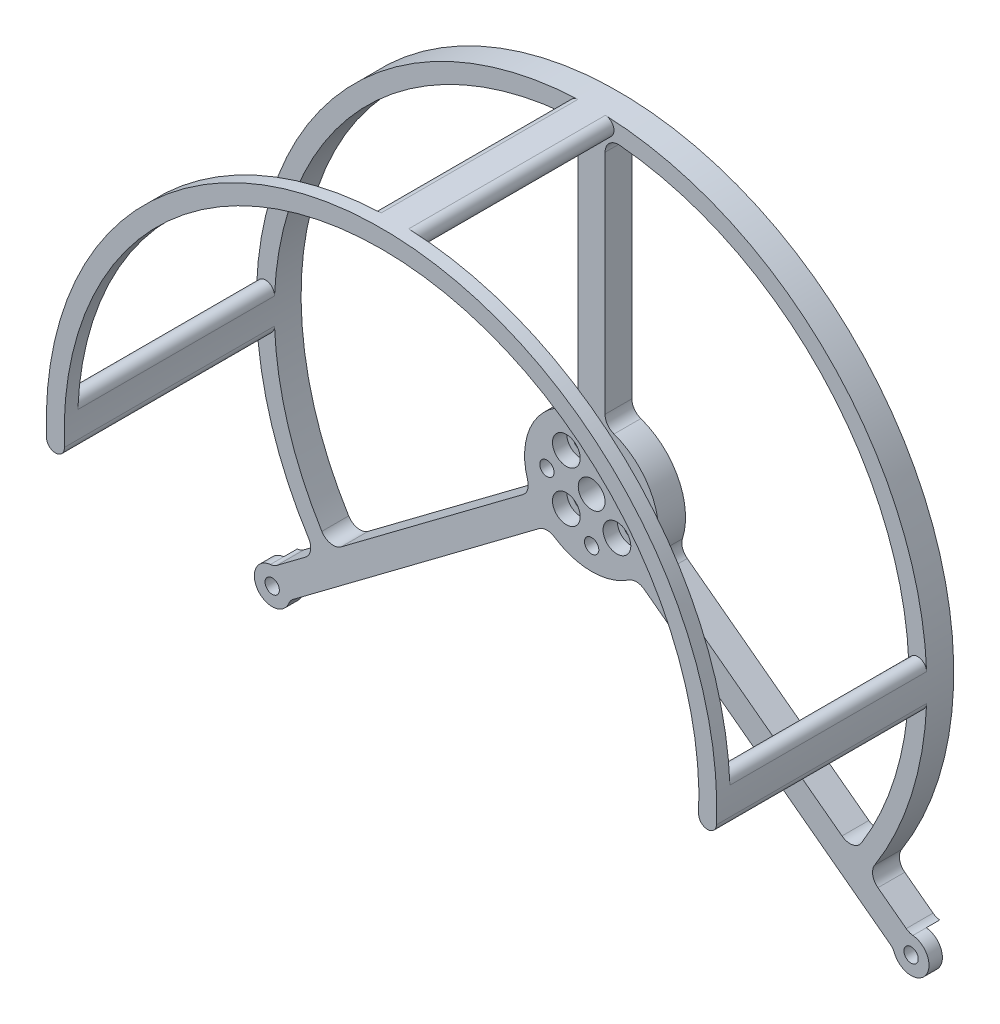
SolidWorks part; units mm, degrees
ref_plane "前视基准面" through (0, 0, 0) normal (0, 0, 1) x (1, 0, 0)
ref_plane "上视基准面" through (0, 0, 0) normal (0, 1, 0) x (1, 0, 0)
ref_plane "右视基准面" through (0, 0, 0) normal (1, 0, 0) x (0, 0, -1)
sketch "草图1" plane through (0, 0, 0) normal (0, 0, 1) x (1, 0, 0)
  line L0 (0, 0) -> (10, 0) construction
  line L1 (0, 0) -> (0, -10) construction
  line L2 (0, 0) -> (5.6569, -5.6569) construction
  circle A0 centre (0, 0) radius 15
  circle A1 centre (0, 0) radius 8 construction
  circle A2 centre (0, 0) radius 10 construction
  circle A3 centre (5.6569, -5.6569) radius 1.6
  circle A4 centre (-5.6569, -5.6569) radius 1.6
  circle A5 centre (5.6569, 5.6569) radius 1.6
  circle A6 centre (-5.6569, 5.6569) radius 1.6
  circle A7 centre (0, -10) radius 1.6
  circle A8 centre (10, 0) radius 1.6
  circle A9 centre (-10, 0) radius 1.6
  circle A10 centre (0, 10) radius 1.6
  dimension "D1" = 30
  dimension "D2" = 16
  dimension "D3" = 20
  dimension "D5" = 3.2
  dimension "D6" = 3.2
extrude "凸台-拉伸1" add sketch "草图1" along normal blind 6
sketch "草图2" plane through (0, 0, 6) normal (0, 0, 1) x (1, 0, 0)
  line L0 (0, 0) -> (8, 0) construction
  line L1 (0, 0) -> (0, -8) construction
  circle A0 centre (0, 0) radius 8 construction
  circle A1 centre (5.6569, 5.6569) radius 3.1
  circle A2 centre (5.6569, -5.6569) radius 3.1
  circle A3 centre (-5.6569, -5.6569) radius 3.1
  circle A4 centre (-5.6569, 5.6569) radius 3.1
  dimension "D1" = 6.2
extrude "切除-拉伸1" cut sketch "草图2" against normal blind 3.2
sketch "草图4" plane through (0, 0, 0) normal (0, 0, -1) x (-1, 0, 0)
  circle A0 centre (0, 0) radius 3
  dimension "D1" = 6
extrude "切除-拉伸2" cut sketch "草图4" against normal blind 8
sketch "草图3" plane through (0, 0, 0) normal (0, 0, -1) x (-1, 0, 0)
  line L0 (0, 0) -> (15, 0) construction
  line L1 (0, 0) -> (55.2216, -41.3712) construction
  line L5 (13.5609, -6.4111) -> (76.4213, -53.5052)
  line L9 (9.9634, -11.213) -> (72.8238, -58.3071)
  line L10 (76.4213, -53.5052) -> (72.8238, -58.3071)
  circle A0 centre (0, 0) radius 66 construction
  circle A1 centre (0, 0) radius 69 construction
  circle A3 centre (0, 0) radius 15 construction
  circle A4 centre (0, 0) radius 15
  circle M4 centre (0, 0) radius 15
  dimension "D1" = 132
  dimension "D2" = 138
  dimension "D3" = 30
  dimension "D5" = 93.29
  dimension "D4" = 3
  dimension "D6" = 36.84
extrude "凸台-拉伸3" add sketch "草图3" against normal blind 6 contours L10 L5 L9 M4 region at (-43.2733, -32.4197, 0)
sketch "草图5" plane through (0, 0, 0) normal (0, 0, -1) x (-1, 0, 0)
  line L0 (0, 0) -> (74.6226, -55.9061) construction
  line L1 (76.4213, -53.5052) -> (72.8238, -58.3071) construction
  circle A0 centre (71.4599, -53.5367) radius 1.6
  circle A1 centre (0, 0) radius 3 construction
  dimension "D1" = 3.2
  dimension "D2" = 89.29
extrude "切除-拉伸3" cut sketch "草图5" against normal blind 6
mirror "镜向2" about plane through (0, 0, 0) normal (1, 0, 0) of "切除-拉伸3", "凸台-拉伸3"
sketch "草图6" plane through (0, 0, 0) normal (0, 0, -1) x (-1, 0, 0)
  circle A0 centre (-71.4599, -53.5367) radius 4
  circle A1 centre (-71.4599, -53.5367) radius 1.6
  circle A2 centre (71.4599, -53.5367) radius 1.6
  circle A3 centre (71.4599, -53.5367) radius 4
  dimension "D1" = 8
  dimension "D2" = 3.2
  dimension "D3" = 8
  dimension "D4" = 3.2
extrude "凸台-拉伸4" add sketch "草图6" against normal blind 6
sketch "草图7" plane through (0, 0, 0) normal (0, 0, -1) x (-1, 0, 0)
  line L0 (-75.3761, -52.7221) -> (-79.5868, -53.5367)
  line L1 (-79.5868, -53.5367) -> (-72.314, -61.4299)
  line L2 (-72.314, -61.4299) -> (-71.8903, -57.5135)
  line L3 (71.7786, -57.524) -> (73.2525, -62.4618)
  line L4 (73.2525, -62.4618) -> (79.8511, -53.0431)
  line L5 (79.8511, -53.0431) -> (75.3761, -52.7221)
  arc A0 (-75.3761, -52.7221) -> (-71.8903, -57.5135) centre (-71.4599, -53.5367) ccw
  arc A1 (71.7786, -57.524) -> (75.3761, -52.7221) centre (71.4599, -53.5367) ccw
extrude "切除-拉伸4" cut sketch "草图7" against normal blind 6 contours A1 L5 L4 L3 | A0 L2 L1 L0
sketch "草图8" plane through (0, 0, 0) normal (0, 0, -1) x (-1, 0, 0)
  line L0 (-58.5702, -40.1314) -> (-61.7742, -42.5318)
  line L1 (-13.5609, -6.4111) -> (-71.1413, -49.5494) construction
  line L2 (61.7742, -42.5318) -> (58.5702, -40.1314)
  line L3 (13.5609, -6.4111) -> (71.1413, -49.5494) construction
  circle A0 centre (0, 0) radius 89.29 construction
  arc A1 (61.7742, -42.5318) -> (-61.7742, -42.5318) centre (0, 0) ccw
  arc A2 (58.5702, -40.1314) -> (-58.5702, -40.1314) centre (0, 0) ccw
  dimension "D1" = 150
  dimension "D2" = 142
extrude "凸台-拉伸5" add sketch "草图8" against normal blind 6
sketch "草图9" plane through (0, 0, 0) normal (0, 0, -1) x (-1, 0, 0)
  line L0 (0, 0) -> (0, 71) construction
  line L1 (-3, 14.6969) -> (-3, 70.9366)
  line L2 (3, 14.6969) -> (3, 70.9366)
  arc A0 (58.5702, -40.1314) -> (-58.5702, -40.1314) centre (0, 0) ccw construction
  arc A1 (13.5609, -6.4111) -> (-13.5609, -6.4111) centre (0, 0) ccw construction
  arc A2 (3, 14.6969) -> (-3, 14.6969) centre (0, 0) ccw
  arc A3 (3, 70.9366) -> (-3, 70.9366) centre (0, 0) ccw
  dimension "D1" = 3
extrude "凸台-拉伸6" add sketch "草图9" against normal blind 6
sketch "草图10" plane through (0, 0, 6) normal (0, 0, 1) x (1, 0, 0)
  line L0 (0, 0) -> (-73, 0) construction
  line L1 (-73, 0) -> (-75, 0) construction
  arc A0 (-72.8288, 4.997) -> (-72.8288, -4.997) centre (0, 0) ccw construction
  arc A1 (-74.9366, 3.0822) -> (-74.9366, -3.0822) centre (0, 0) ccw
  arc A10 (-70.94, 2.9178) -> (-70.94, -2.9178) centre (0, 0) ccw
  arc A11 (-70.94, 2.9178) -> (-74.9366, 3.0822) centre (-72.9383, 3) ccw
  arc A12 (-70.94, -2.9178) -> (-74.9366, -3.0822) centre (-72.9383, -3) cw
  arc A13 (2.9178, 70.94) -> (-2.9178, 70.94) centre (0, 0) ccw
  arc A14 (-2.9178, 70.94) -> (-3.0822, 74.9366) centre (-3, 72.9383) cw
  arc A15 (3.0822, 74.9366) -> (-3.0822, 74.9366) centre (0, 0) ccw
  arc A16 (2.9178, 70.94) -> (3.0822, 74.9366) centre (3, 72.9383) ccw
  arc A17 (70.94, -2.9178) -> (70.94, 2.9178) centre (0, 0) ccw
  arc A18 (70.94, 2.9178) -> (74.9366, 3.0822) centre (72.9383, 3) cw
  arc A19 (74.9366, -3.0822) -> (74.9366, 3.0822) centre (0, 0) ccw
  arc A20 (70.94, -2.9178) -> (74.9366, -3.0822) centre (72.9383, -3) ccw
  arc A25 (-2.9178, -70.94) -> (2.9178, -70.94) centre (0, 0) ccw [skipped]
  arc A26 (2.9178, -70.94) -> (3.0822, -74.9366) centre (3, -72.9383) cw [skipped]
  arc A27 (-3.0822, -74.9366) -> (3.0822, -74.9366) centre (0, 0) ccw [skipped]
  arc A28 (-2.9178, -70.94) -> (-3.0822, -74.9366) centre (-3, -72.9383) ccw [skipped]
  point P33 (0, 0)
  dimension "D1" = 146
  dimension "D2" = 3
  dimension "D3" = 71
  dimension "D4" = 75
  dimension "D5" = 2
  dimension "D6" = 73
  dimension "D7" = 4
extrude "凸台-拉伸7" add sketch "草图10" along normal blind 44
sketch "草图11" plane through (0, 0, 50) normal (0, 0, 1) x (1, 0, 0)
  arc A0 (70.94, -2.9178) -> (-70.94, -2.9178) centre (0, 0) ccw
  arc A1 (74.9366, -3.0822) -> (-74.9366, -3.0822) centre (0, 0) ccw
  arc A2 (70.94, -2.9178) -> (74.9366, -3.0822) centre (72.9383, -3) ccw
  arc A3 (-74.9366, -3.0822) -> (-70.94, -2.9178) centre (-72.9383, -3) ccw
  dimension "D1" = 75
  dimension "D2" = 2
  dimension "D3" = 2
extrude "凸台-拉伸8" add sketch "草图11" along normal blind 3
fillet "圆角5" radius 3 14 edges at (-58.5702, -40.1314, 3) (-13.5609, -6.4111, 3) (-3, 14.6969, 3) (3, 14.6969, 3) (13.5609, -6.4111, 3) (58.5702, -40.1314, 3) (61.7742, -42.5318, 3) (71.1413, -49.5494, 3) (67.5438, -54.3513, 3) (9.9634, -11.213, 3) (-9.9634, -11.213, 3) (-71.1413, -49.5494, 3) (-67.5438, -54.3513, 3) (-61.7742, -42.5318, 3)
sketch "草图12" plane through (0, 0, 6) normal (0, 0, 1) x (1, 0, 0)
  line L0 (74.5576, -56.0674) -> (72.1117, -59.0614)
  line L1 (72.1117, -59.0614) -> (69.5336, -58.7202)
  line L2 (69.5336, -58.7202) -> (69.7416, -57.1488)
  arc A0 (69.7416, -57.1488) -> (74.5576, -56.0674) centre (71.4599, -53.5367) ccw
extrude "切除-拉伸5" cut sketch "草图12" against normal blind 40 contours A0 L0 L1 L2
fillet "圆角6" radius 3 2 edges at (3, 70.9366, 3) (-3, 70.9366, 3)
ref_plane "基准面1" through (0, 0, 3) normal (0, 0, -1) x (-1, 0, 0)
sketch "草图14" plane through (0, 0, 0) normal (0, 0, -1) x (-1, 0, 0)
  circle A0 centre (-71.4599, -53.5367) radius 4
  circle A1 centre (71.4599, -53.5367) radius 4
  dimension "D1" = 8
  dimension "D2" = 8
extrude "切除-拉伸7" cut sketch "草图14" against normal blind 3
